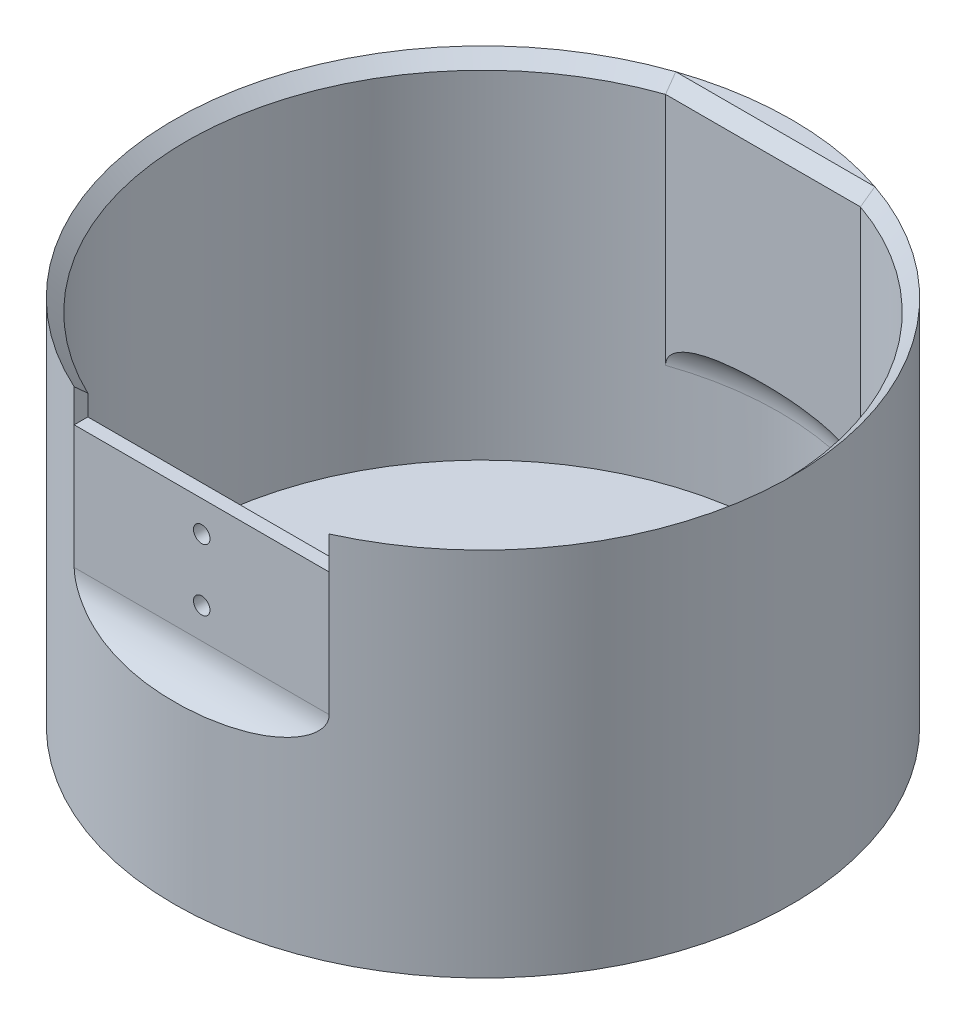
SolidWorks part; units mm, degrees
ref_plane "Front Plane" through (0, 0, 0) normal (0, 0, 1) x (1, 0, 0)
ref_plane "Top Plane" through (0, 0, 0) normal (0, 1, 0) x (1, 0, 0)
ref_plane "Right Plane" through (0, 0, 0) normal (1, 0, 0) x (0, 0, -1)
sketch "Sketch1" plane through (0, 0, 0) normal (0, 1, 0) x (1, 0, 0)
  circle A0 centre (0, 0) radius 75
  dimension "D1" = 150
extrude "Boss-Extrude1" add sketch "Sketch1" along normal blind 5
sketch "Sketch2" plane through (0, 5, 0) normal (0, 1, 0) x (1, 0, 0)
  circle A0 centre (0, 0) radius 72
  circle A1 centre (0, 0) radius 75
  circle A2 centre (0, 0) radius 75
  dimension "D1" = 0
  dimension "D2" = 3
extrude "Boss-Extrude2" add sketch "Sketch2" along normal blind 85
sketch "Sketch3" plane through (0, 90, 0) normal (0, 1, 0) x (1, 0, 0)
  line L0 (-31.6386, 68) -> (31.6386, 68)
  line L2 (-37.4166, -65) -> (37.4166, -65)
  circle A0 centre (0, 0) radius 75 construction
  arc A1 (31.6386, 68) -> (-31.6386, 68) centre (0, 0) ccw
  arc A2 (-37.4166, -65) -> (37.4166, -65) centre (0, 0) ccw
  arc A4 (31.6386, 68) -> (-31.6386, 68) centre (0, 0) ccw
  circle M3 centre (0, 0) radius 75
  circle M4 centre (0, 0) radius 72
  dimension "D2" = 65
  dimension "D1" = 68
extrude "Boss-Extrude3" add sketch "Sketch3" against normal blind 50 contours L0 M4 | L0 M3 M4 | L2 M3 M4 | L2 M4 region at (0, 90, -74.3634) region at (0, 90, -69.6039) region at (-34.1921, 90, 65.755) region at (0, 90, 67.812)
ref_plane "Plane1" through (0, 85, 0) normal (0, 1, 0) x (1, 0, 0)
fillet "Fillet1" radius 10 1 edges at (0, 40, 72)
fillet "Fillet2" radius 10 1 edges at (0, 40, -72)
sketch "Sketch7" plane through (0, 0, 65) normal (0, 0, -1) x (-1, 0, 0)
  line L0 (30.9677, 90) -> (30.9677, 30) construction
  line L1 (-30.9677, 90) -> (30.9677, 90)
  line L2 (-30.9677, 90) -> (-30.9677, 82)
  line L3 (-30.9677, 82) -> (30.9677, 82)
  line L4 (30.9677, 90) -> (30.9677, 82)
  dimension "D1" = 8
extrude "Cut-Extrude1" cut sketch "Sketch7" against normal up to surface (3.3081 mm away) contours L3 L4 L1 L2 up to face at (0, 90, 75)
chamfer "Chamfer1" distance 3 angle 45 1 edges at (71.8917, 90, -3.9478)
chamfer "Chamfer2" distance 3 angle 45 2 edges at (-71.8917, 90, -3.9478) (3.9871, 90, -68)
sketch "Sketch8" plane through (0, 82, 0) normal (0, 1, 0) x (1, 0, 0)
  line L3 (-30.9677, -68.3081) -> (30.9677, -68.3081)
  arc A0 (-30.9677, -68.3081) -> (30.9677, -68.3081) centre (0, 0) ccw construction
  arc A1 (-30.9677, -68.3081) -> (30.9677, -68.3081) centre (0, 0) ccw
extrude "Cut-Extrude2" cut sketch "Sketch8" against normal blind 40
fillet "Fillet3" radius 10 1 edges at (0, 42, 68.3081)
sketch "Sketch10" plane through (0, 0, 68.3081) normal (0, 0, 1) x (1, 0, 0)
  line L0 (-30.9677, 67) -> (30.9677, 67) construction
  line L1 (-30.9677, 52) -> (-30.9677, 82) construction
  line L2 (30.9677, 52) -> (30.9677, 82) construction
  point P0 (0, 74.5)
  point P2 (0, 59.5)
  point P15 (0, 0)
  point P16 (0, 0)
  dimension "D1" = 7.5
  dimension "D2" = 7.5
hole_wizard "Ø4.0mm Dowel Hole1" positions "Sketch10" profile "Sketch11" hole size "Ø4.0" standard "ISO"
sketch "Sketch11" plane through (0, 74.5, 68.3081) normal (1, 0, 0) x (0, -1, 0)
  line L0 (0, 0) -> (0, 4.5098)
  line L1 (0, 4.5098) -> (2, 3.3081)
  line L2 (2, 3.3081) -> (2, 0)
  line L5 (2, 0) -> (0, 0)
  line L10 (0, 4.5098) -> (-2, 3.3081) construction
  line L11 (0, -6.35) -> (0, 107.95) construction
  dimension "Hole Dia." = 4
  dimension "Hole Depth" = 3.3081
  dimension "Drill Angle" = 118
